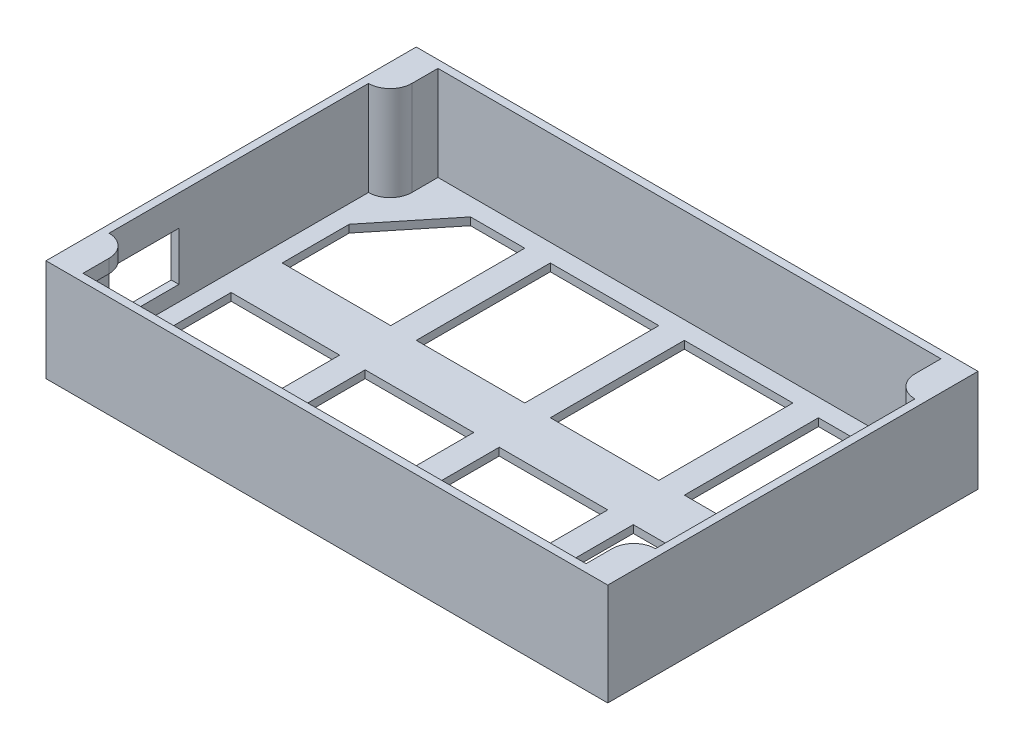
SolidWorks part; units mm, degrees
note: The reader was unsure of these and kept them because the rebuilt part matched: shared geometry of "Sketch3<6>".
ref_plane "Front Plane" through (0, 0, 0) normal (0, 0, 1) x (1, 0, 0)
ref_plane "Top Plane" through (0, 0, 0) normal (0, 1, 0) x (1, 0, 0)
ref_plane "Right Plane" through (0, 0, 0) normal (1, 0, 0) x (0, 0, -1)
sketch "Sketch1" plane through (0, 0, 0) normal (0, 1, 0) x (1, 0, 0)
  line L0 (110, 145) -> (110, 0) construction
  line L1 (0, 0) -> (220, 0)
  line L2 (0, 0) -> (0, 145)
  line L3 (0, 145) -> (220, 145)
  line L4 (220, 0) -> (220, 145)
  line L7 (10, 82.5) -> (52.5, 82.5)
  line L8 (52.5, 135) -> (52.5, 82.5)
  line L9 (62.5, 135) -> (105, 135)
  line L10 (62.5, 135) -> (62.5, 82.5)
  line L11 (62.5, 82.5) -> (105, 82.5)
  line L12 (105, 135) -> (105, 82.5)
  line L13 (110, 72.5) -> (0, 72.5) construction
  line L14 (52.5, 135) -> (62.5, 135) construction
  line L15 (62.5, 82.5) -> (62.5, 72.5) construction
  line L16 (10, 82.5) -> (10, 108.75)
  line L17 (10, 135) -> (0, 135) construction
  line L18 (10, 135) -> (10, 145) construction
  line L19 (10, 145) -> (0, 145) construction
  line L20 (0, 135) -> (0, 145) construction
  line L21 (10, 108.75) -> (31.25, 135)
  line L22 (31.25, 135) -> (52.5, 135)
  line L23 (10, 135) -> (10, 108.75) construction
  line L24 (10, 135) -> (31.25, 135) construction
  line L25 (62.5, 62.5) -> (105, 62.5)
  line L26 (105, 10) -> (105, 62.5)
  line L27 (62.5, 10) -> (105, 10)
  line L28 (62.5, 10) -> (62.5, 62.5)
  line L29 (10, 36.25) -> (31.25, 10)
  line L30 (10, 62.5) -> (10, 36.25)
  line L31 (10, 62.5) -> (52.5, 62.5)
  line L32 (52.5, 10) -> (52.5, 62.5)
  line L33 (31.25, 10) -> (52.5, 10)
  line L34 (210, 62.5) -> (210, 36.25)
  line L35 (210, 62.5) -> (167.5, 62.5)
  line L36 (167.5, 10) -> (167.5, 62.5)
  line L37 (188.75, 10) -> (167.5, 10)
  line L38 (210, 36.25) -> (188.75, 10)
  line L39 (157.5, 10) -> (157.5, 62.5)
  line L40 (157.5, 10) -> (115, 10)
  line L41 (115, 10) -> (115, 62.5)
  line L42 (157.5, 62.5) -> (115, 62.5)
  line L43 (157.5, 82.5) -> (115, 82.5)
  line L44 (115, 135) -> (115, 82.5)
  line L45 (157.5, 135) -> (115, 135)
  line L46 (157.5, 135) -> (157.5, 82.5)
  line L47 (210, 108.75) -> (188.75, 135)
  line L48 (210, 82.5) -> (210, 108.75)
  line L49 (210, 82.5) -> (167.5, 82.5)
  line L50 (167.5, 135) -> (167.5, 82.5)
  line L51 (188.75, 135) -> (167.5, 135)
  point P23 (31.25, 82.5)
  point P25 (52.5, 108.75)
  dimension "D1" = 145
  dimension "D2" = 220
  dimension "D3" = 10
  dimension "D4" = 10
  dimension "D5" = 5
  dimension "D6" = 10
extrude "Boss-Extrude1" add sketch "Sketch1" along normal blind 3
sketch "Sketch2" plane through (0, 3, 0) normal (0, 1, 0) x (1, 0, 0)
  line L9 (0, 0) -> (0, 145)
  line L10 (0, 72.5) -> (3, 72.5) construction
  line L11 (3, 123.3) -> (3, 21.7)
  line L12 (11.5, 13.2) -> (11.5, 3)
  line L13 (0, 145) -> (0, 0) construction
  line L14 (0, 0) -> (220, 0) construction
  line L18 (11.5, 3) -> (208.5, 3)
  line L19 (110, 3) -> (110, 0) construction
  line L24 (220, 0) -> (0, 0)
  line L25 (110, 142) -> (110, 145) construction
  line L26 (220, 145) -> (0, 145)
  line L27 (11.5, 142) -> (208.5, 142)
  line L28 (11.5, 131.8) -> (11.5, 142)
  line L29 (220, 72.5) -> (217, 72.5) construction
  line L30 (208.5, 131.8) -> (208.5, 142)
  line L31 (208.5, 13.2) -> (208.5, 3)
  line L32 (217, 123.3) -> (217, 21.7)
  line L33 (220, 0) -> (220, 145)
  arc A4 (3, 21.7) -> (11.5, 13.2) centre (3, 13.2) cw
  arc A5 (3, 123.3) -> (11.5, 131.8) centre (3, 131.8) ccw
  arc A6 (217, 123.3) -> (208.5, 131.8) centre (217, 131.8) cw
  arc A7 (217, 21.7) -> (208.5, 13.2) centre (217, 13.2) ccw
  point P21 (0, 72.5)
  point P24 (110, 0)
  dimension "D1" = 3
  dimension "D2" = 8.5
  dimension "D3" = 18.7
extrude "Boss-Extrude2" add sketch "Sketch2" along direction (0, -1, 0) on the side of the normal offset from surface (37 mm away) 40
sketch "Sketch3" plane through (3, 0, 0) normal (-1, 0, 0) x (0, 0, 1)
  line L0 (-3, 40) -> (-3, 3) construction
  line L1 (0, 0) -> (-3, 0) construction
  line L2 (0, 0) -> (0, 3) construction
  line L3 (0, 3) -> (-3, 3) construction
  line L4 (-3, 0) -> (-3, 3) construction
  line L5 (-3, 3) -> (-56.975, 3)
  line L6 (-3, 3) -> (-3, 34.75)
  line L7 (-3, 34.75) -> (-56.975, 34.75)
  line L8 (-56.975, 3) -> (-56.975, 34.75)
  line L9 (-123.3, 3) -> (-21.7, 3) construction
  line L10 (-145, 3) -> (-3, 3) construction
  line L11 (-3, 40) -> (-3, 3) construction
  line L12 (-145, 40) -> (-145, 0) construction
  line L14 (-49.0375, 28.0031) -> (-21.2562, 28.0031)
  line L15 (-49.0375, 28.0031) -> (-49.0375, 8.9531)
  line L16 (-49.0375, 8.9531) -> (-21.2562, 8.9531)
  line L17 (-21.2562, 28.0031) -> (-21.2562, 8.9531)
  line M28 (-21.7, 40) -> (-21.7, 3)
  dimension "D1" = 53.975
  dimension "D2" = 31.75
  dimension "D3" = 27.7812
  dimension "D4" = 19.05
  dimension "D5" = 7.9375
  dimension "D6" = 6.7469
extrude "Cut-Extrude1" cut sketch "Sketch3" along normal up to surface (3 mm away) contours L16 L15 L14 M28 | L8 L7 L6 L5
extrude "Cut-Extrude2" cut sketch "Sketch3<6>" against normal up to surface (8.5 mm away) contours L7 L8 L5 L6 up to face at (11.5, 21.5, -8.1)
sketch "Sketch3<6>" plane through (3, 0, 0) normal (-1, 0, 0) x (0, 0, 1) same geometry as "Sketch3"
